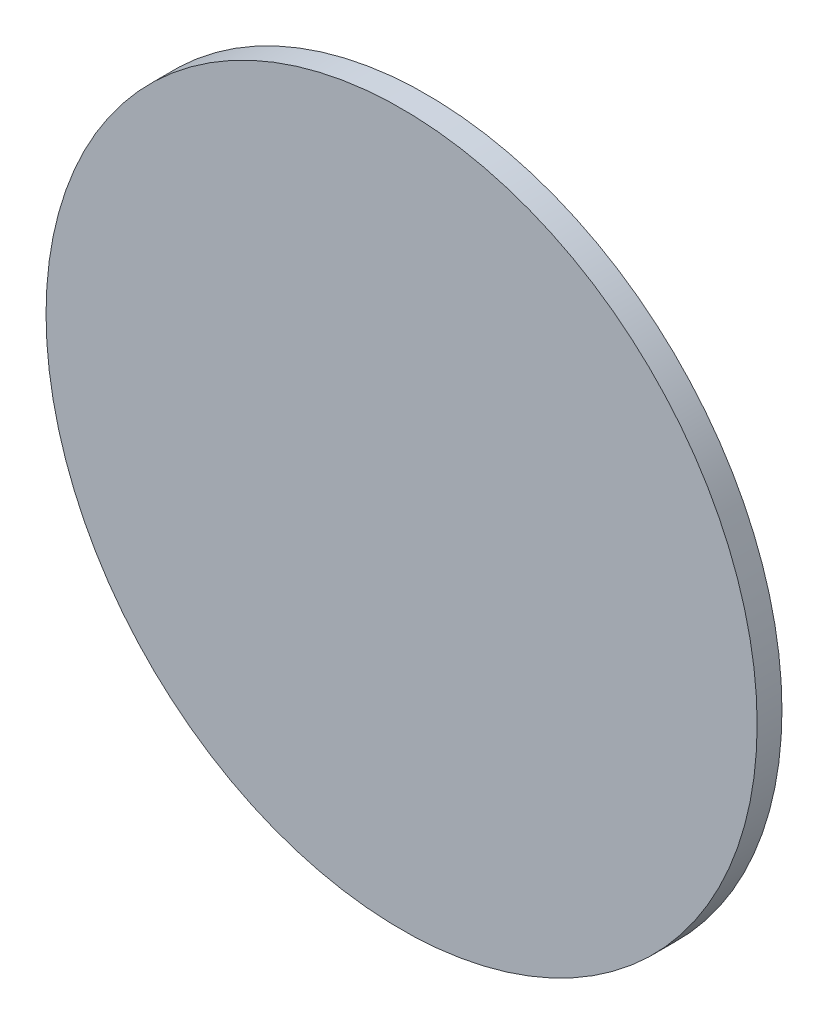
SolidWorks part; units mm, degrees
material "POM Acetal Copolymer"
ref_plane "Front Plane" through (0, 0, 0) normal (0, 0, 1) x (1, 0, 0)
ref_plane "Top Plane" through (0, 0, 0) normal (0, 1, 0) x (1, 0, 0)
ref_plane "Right Plane" through (0, 0, 0) normal (1, 0, 0) x (0, 0, -1)
sketch "Extrude sketch 1" plane through (0, 0, 0) normal (0, 0, 1) x (1, 0, 0)
  circle A0 centre (757.5, 0) radius 86
  dimension "D1" = 172
extrude "Extrude 1" add sketch "Extrude sketch 1" along normal blind 6 from offset 317 separate body
sketch "Extrude sketch 2" plane through (0, 0, 0) normal (0, 0, 1) x (1, 0, 0)
  circle A0 centre (757.5, 0) radius 10
  dimension "D1" = 20
extrude "Extrude 2" add sketch "Extrude sketch 2" along normal blind 8 from offset 309 separate body
combine bodies "Combine (weld / assembly of features)" operation type add bodies to combine 101 102
